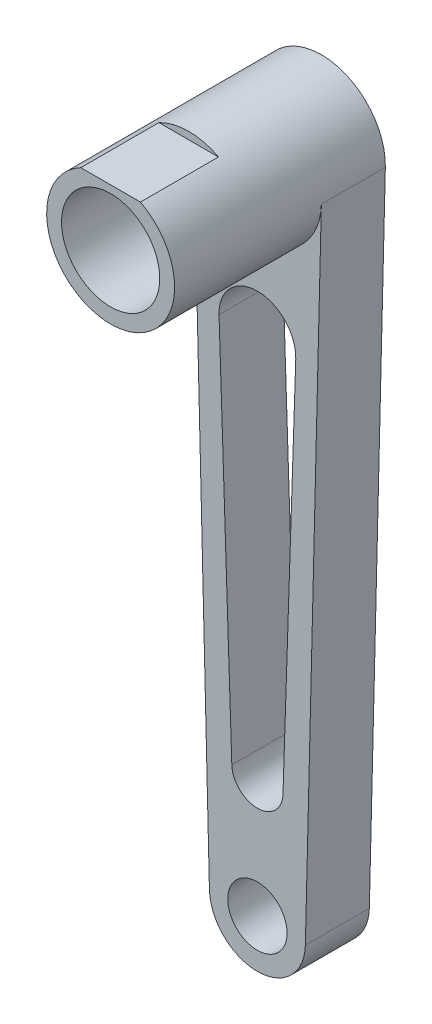
SolidWorks part; units mm, degrees
material "PEI"
ref_plane "Front Plane" through (0, 0, 0) normal (0, 0, 1) x (1, 0, 0)
ref_plane "Top Plane" through (0, 0, 0) normal (0, 1, 0) x (1, 0, 0)
ref_plane "Right Plane" through (0, 0, 0) normal (1, 0, 0) x (0, 0, -1)
sketch "Sketch1" plane through (0, 0, 0) normal (0, 0, 1) x (1, 0, 0)
  line L0 (-10.294, 11.8201) -> (-7.347, -107.9077)
  line L1 (0, -101.6) -> (0, 0) construction
  line L2 (7.347, -107.9067) -> (10.2653, 10.6574)
  line L3 (6.244, -15.7837) -> (3.867, -87.0546)
  line L4 (-6.2592, -15.3276) -> (-3.8401, -87.8596)
  circle A0 centre (0, 0) radius 10
  circle A1 centre (0, 0) radius 7.675
  circle A2 centre (0, -101.6) radius 7.5
  circle A3 centre (0, -101.6) radius 4.635
  circle A6 centre (0, -23) radius 6
  circle A7 centre (0, -83) radius 4
  dimension "D1" = 15.35
  dimension "D2" = 20
  dimension "D3" = 15
  dimension "D5" = 9.27
  dimension "D7" = 12
  dimension "D8" = 60
  dimension "D9" = 23
  dimension "D6" = 8
  dimension "D4" = 101.6
extrude "Boss-Extrude2" add sketch "Sketch1" along normal blind 10 contours L1 A2 L2 A0 | A2 L1 A0 L0 | A3 A2 region at (0, -11.0349, 0) region at (-0.0897, -94.3127, 0)
extrude "Boss-Extrude3" add sketch "Sketch1<6>" along normal blind 32.94 contours A0 A1 region at (-0.1196, 9.7164, 0)
sketch "Sketch1<6>" plane through (0, 0, 0) normal (0, 0, 1) x (1, 0, 0) same geometry as "Sketch1"
sketch "Sketch2" plane through (0, 0, 32.94) normal (0, 0, 1) x (1, 0, 0)
  line L0 (-10.0333, 8.85) -> (9.9921, 8.85)
  line L1 (9.9921, 8.85) -> (9.9921, 18.6582)
  line L2 (9.9921, 18.6582) -> (-10.0333, 18.6582)
  line L3 (-10.0333, 18.6582) -> (-10.0333, 8.85)
  circle A0 centre (0, 0) radius 10 construction
  point P3 (-0.0206, 8.85)
  dimension "D1" = 8.85
extrude "Cut-Extrude1" cut sketch "Sketch2" against normal blind 12.2
